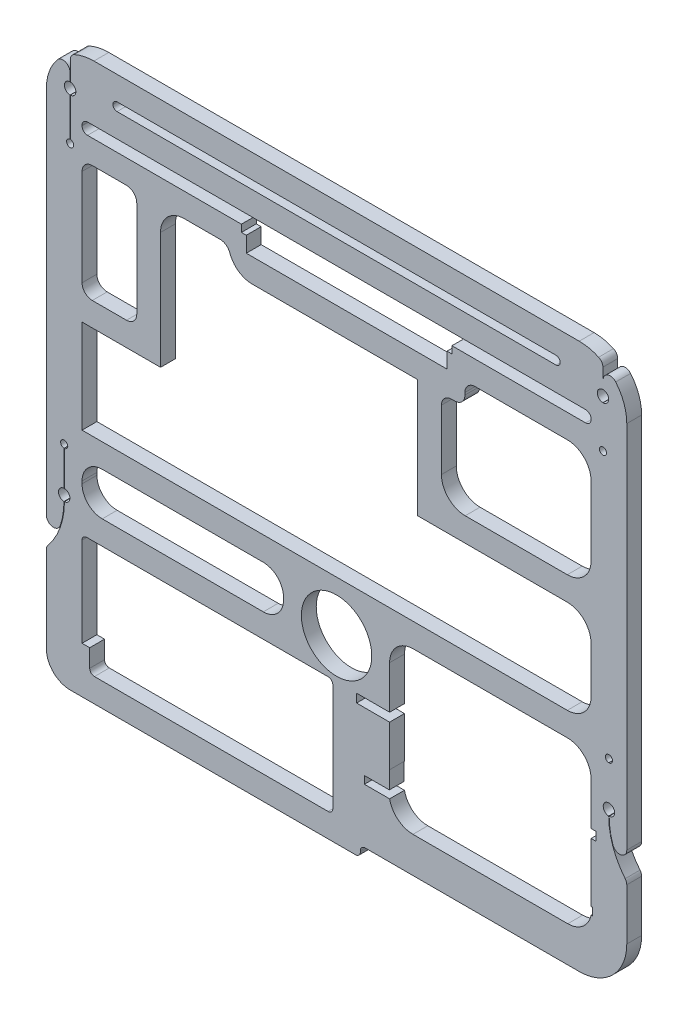
SolidWorks part; units mm, degrees
ref_plane "Front Plane" through (0, 0, 0) normal (0, 0, 1) x (1, 0, 0)
ref_plane "Top Plane" through (0, 0, 0) normal (0, 1, 0) x (1, 0, 0)
ref_plane "Right Plane" through (0, 0, 0) normal (1, 0, 0) x (0, 0, -1)
sketch "Sketch1" plane through (0, 0, 0) normal (0, 0, 1) x (1, 0, 0)
  line L0 (63.9883, 61.406) -> (63.9883, 57.596) construction
  line L1 (11.1776, 3.1158) -> (73.1542, 3.1158)
  line L2 (11.1776, 3.1158) -> (11.1776, 61.406)
  line L3 (11.1776, 61.406) -> (73.1542, 61.406)
  line L4 (73.1542, 3.1158) -> (73.1542, 61.406)
  line L5 (69.3442, 57.596) -> (14.9876, 57.596)
  line L6 (69.3442, 57.596) -> (69.3442, 6.9258)
  line L7 (69.3442, 6.9258) -> (14.9876, 6.9258)
  line L8 (14.9876, 57.596) -> (14.9876, 6.9258)
  line L9 (63.9883, 59.501) -> (18.0707, 59.501) construction
  line L10 (14.9876, 39.3805) -> (11.1776, 39.3805) construction
  line L11 (13.0826, 39.3805) -> (13.0826, 23.9527) construction
  line L12 (13.5248, 6.9258) -> (13.5248, 3.1158) construction
  line L13 (13.5248, 5.0208) -> (21.1598, 5.0208) construction
  line L14 (73.1542, 38.1916) -> (69.3442, 38.1916) construction
  line L15 (71.2492, 38.1916) -> (71.2492, 22.3321) construction
  line L16 (55.7422, 59.501) -> (30.5962, 59.501) construction
  line L19 (42.3087, 5.0208) -> (41.7626, 5.0208) construction
  line L21 (69.3442, 27.6227) -> (69.3442, 52.516) construction
  line L22 (14.9876, 47.563) -> (14.9876, 27.6227) construction
  dimension "D1" = 3.81
  dimension "D2" = 3.81
extrude "Boss-Extrude1" add sketch "Sketch1" along normal blind 1.5875
sketch "Sketch2" plane through (0, 0, 0) normal (0, 0, -1) x (-1, 0, 0)
  line L0 (-69.3442, 6.9258) -> (-69.3442, 57.596) construction
  line L1 (-69.3442, 26.6348) -> (-14.9876, 26.6348)
  line L2 (-69.3442, 26.6348) -> (-69.3442, 24.0948)
  line L3 (-69.3442, 24.0948) -> (-14.9876, 24.0948)
  line L4 (-14.9876, 26.6348) -> (-14.9876, 24.0948)
  line L5 (-14.9876, 57.596) -> (-14.9876, 6.9258) construction
  line L6 (-20.1206, 26.6348) -> (-57.8206, 26.6348) construction
  line L7 (-53.9642, 53.4304) -> (-53.9642, 51.7667)
  line L8 (-32.5266, 53.4304) -> (-32.0059, 53.4304)
  line L9 (-32.5266, 51.7667) -> (-53.9642, 51.7667) construction
  line L10 (-32.5266, 51.7667) -> (-32.5266, 53.4304) construction
  line L11 (-69.3442, 54.1924) -> (-54.4849, 54.1924)
  line L12 (-69.3442, 54.1924) -> (-69.3442, 51.6524)
  line L13 (-69.3442, 51.6524) -> (-55.8692, 51.6524)
  line L14 (-14.9876, 54.1924) -> (-14.9876, 51.6524)
  line L15 (-69.3442, 57.596) -> (-14.9876, 57.596)
  line L16 (-69.3442, 57.596) -> (-69.3442, 55.4243)
  line L17 (-69.3442, 55.4243) -> (-14.9876, 55.4243)
  line L18 (-14.9876, 57.596) -> (-14.9876, 55.4243)
  line L19 (-69.3442, 57.596) -> (-14.9876, 57.596) construction
  line L20 (-54.4849, 54.1924) -> (-54.4849, 53.4304)
  line L21 (-62.3462, 55.4243) -> (-23.9922, 55.4243) construction
  line L22 (-54.4849, 53.4304) -> (-53.9642, 53.4304)
  line L23 (-32.5266, 51.7667) -> (-53.9642, 51.7667)
  line L24 (-32.5266, 51.7667) -> (-32.5266, 53.4304)
  line L25 (-55.8692, 51.6524) -> (-55.8692, 49.2267)
  line L26 (-55.8692, 49.2267) -> (-30.6216, 49.2267)
  line L27 (-30.6216, 49.2267) -> (-30.6216, 51.6524)
  line L28 (-30.6216, 51.6524) -> (-14.9876, 51.6524)
  line L29 (-32.0059, 53.4304) -> (-32.0059, 54.1924)
  line L30 (-62.3462, 54.1924) -> (-23.9922, 54.1924) construction
  line L32 (-54.4849, 53.4304) -> (-54.4849, 54.1924) construction
  line L33 (-32.0059, 53.4304) -> (-54.4849, 53.4304) construction
  line L34 (-32.0059, 54.1924) -> (-14.9876, 54.1924)
  line L36 (-32.0059, 53.4304) -> (-32.0059, 54.1924) construction
  line L37 (-32.5266, 51.7667) -> (-32.5266, 53.4304) construction
  dimension "D1" = 2.54
  dimension "D2" = 1.905
  dimension "D3" = 2.54
  dimension "D4" = 1.905
  dimension "D5" = 2.54
extrude "Boss-Extrude2" add sketch "Sketch2" against normal up to surface (1.5875 mm away) up to face at (42.1659, 32.2609, 1.5875)
sketch "Sketch3" plane through (0, 0, 0) normal (0, 0, -1) x (-1, 0, 0)
  line L0 (-57.8206, 36.6348) -> (-50.8206, 36.6348) construction
  line L1 (-57.8206, 36.6348) -> (-50.8206, 36.6348)
  line L2 (-57.8206, 36.6348) -> (-69.3442, 36.6348)
  line L3 (-69.3442, 26.6348) -> (-69.3442, 51.6524) construction
  line L4 (-69.3442, 36.6348) -> (-69.3442, 39.1748)
  line L5 (-69.3442, 39.1748) -> (-53.3606, 39.1748)
  line L6 (-50.8206, 28.408) -> (-50.8206, 36.6348)
  line L7 (-50.8206, 28.408) -> (-50.8206, 49.2267)
  line L8 (-55.8692, 49.2267) -> (-30.6216, 49.2267) construction
  line L9 (-50.8206, 49.2267) -> (-53.3606, 49.2267)
  line L10 (-53.3606, 49.2267) -> (-53.3606, 39.1748)
  line L11 (-23.3706, 36.6348) -> (-20.1206, 36.6348) construction
  line L12 (-23.3706, 36.6348) -> (-20.1206, 36.6348)
  line L13 (-20.1206, 36.6348) -> (-14.9876, 36.6348)
  line L14 (-14.9876, 51.6524) -> (-14.9876, 26.6348) construction
  line L15 (-14.9876, 36.6348) -> (-14.9876, 39.1748)
  line L16 (-14.9876, 39.1748) -> (-20.8306, 39.1748)
  line L17 (-20.8306, 39.1748) -> (-20.8306, 51.6524)
  line L18 (-30.6216, 51.6524) -> (-14.9876, 51.6524) construction
  line L19 (-20.8306, 51.6524) -> (-23.3706, 51.6524)
  line L20 (-23.3706, 51.6524) -> (-23.3706, 36.6348)
  line L21 (-23.3706, 36.6348) -> (-16.2412, 25.8471)
  line M22 (-69.3442, 26.6348) -> (-69.3442, 51.6524)
  line M25 (-55.8692, 49.2267) -> (-30.6216, 49.2267)
  line M27 (-30.6216, 51.6524) -> (-14.9876, 51.6524)
  line M28 (-14.9876, 51.6524) -> (-14.9876, 26.6348)
  dimension "D1" = 2.54
  dimension "D2" = 2.54
  dimension "D3" = 2.54
  dimension "D4" = 2.54
extrude "Boss-Extrude3" add sketch "Sketch3" against normal up to surface (1.5875 mm away) contours L10 L5 L2 L1 L6 L7 M25 M22 | L20 L12 L13 L16 L17 M27 M28 region at (63.5824, 36.8588, 0) region at (20.9265, 42.3962, 0) up to face at (42.8855, 53.7395, 1.5875)
sketch "Sketch4" plane through (0, 0, 0) normal (0, 0, -1) x (-1, 0, 0)
  line L0 (-69.3442, 24.0948) -> (-14.9876, 24.0948) construction
  line L1 (-47.8301, 24.0948) -> (-36.5017, 24.0948)
  line L2 (-47.8301, 24.0948) -> (-47.8301, 6.9258)
  line L3 (-47.8301, 6.9258) -> (-36.5017, 6.9258)
  line L4 (-36.5017, 24.0948) -> (-36.5017, 6.9258)
  line L5 (-14.9876, 6.9258) -> (-69.3442, 6.9258) construction
  line L6 (-45.9251, 21.2246) -> (-47.8301, 21.2246) construction
  line L7 (-38.4067, 21.2246) -> (-36.5017, 21.2246) construction
  circle A0 centre (-42.1659, 21.2246) radius 3.7592 construction
  dimension "D1" = 1.905
extrude "Boss-Extrude4" add sketch "Sketch4" against normal up to surface (1.5875 mm away) up to face at (17.9091, 45.4136, 1.5875)
sketch "Sketch5" plane through (0, 0, 0) normal (0, 0, -1) x (-1, 0, 0)
  line L0 (-15.8038, 16.9715) -> (-41.7626, 16.9715) construction
  line L3 (-41.7626, 4.5128) -> (-41.7626, 16.9715) construction
  line L4 (-15.8038, 4.5128) -> (-41.7626, 4.5128) construction
  line L5 (-15.8038, 4.5128) -> (-15.8038, 16.9715) construction
  line L6 (-15.8038, 16.9715) -> (-41.7626, 16.9715)
  line L7 (-41.7626, 4.5128) -> (-41.7626, 16.9715)
  line L8 (-15.8038, 4.5128) -> (-41.7626, 4.5128)
  line L9 (-15.8038, 4.5128) -> (-15.8038, 16.9715)
  circle A0 centre (-42.1659, 21.2246) radius 3.7592 construction
  circle A1 centre (-42.1659, 21.2246) radius 3.7592
extrude "Cut-Extrude1" cut sketch "Sketch5" against normal up to surface (1.5875 mm away) up to face at (58.5871, 15.5103, 1.5875)
sketch "Sketch8" plane through (0, 0, 0) normal (0, 0, -1) x (-1, 0, 0)
  line L1 (-36.5017, 16.9715) -> (-14.9876, 16.9715)
  line L2 (-36.5017, 16.9715) -> (-36.5017, 19.5115)
  line L3 (-36.5017, 19.5115) -> (-14.9876, 19.5115)
  line L4 (-14.9876, 16.9715) -> (-14.9876, 19.5115)
  line L5 (-14.9876, 24.0948) -> (-14.9876, 6.9258) construction
  dimension "D1" = 2.54
extrude "Boss-Extrude5" add sketch "Sketch8" against normal up to surface (1.5875 mm away) up to face at (38.4067, 21.2246, 1.5875)
fillet "Fillet1" radius 5.08 3 edges at (73.1542, 3.1158, 0.7937) (11.1776, 61.406, 0.7937) (73.1542, 61.406, 0.7937)
fillet "Fillet2" radius 2.54 7 edges at (23.3706, 51.6524, 0.7937) (30.6216, 49.2267, 0.7937) (69.3442, 51.6524, 0.7937) (53.3606, 39.1748, 0.7937) (69.3442, 26.6348, 0.7937) (69.3442, 39.1748, 0.7937) (69.3442, 36.6348, 0.7937)
fillet "Fillet3" radius 1.0922 8 edges at (53.3606, 49.2267, 0.7937) (55.8692, 49.2267, 0.7937) (55.8692, 51.6524, 0.7937) (14.9876, 39.1748, 0.7937) (20.8306, 39.1748, 0.7937) (14.9876, 51.6524, 0.7937) (20.8306, 51.6524, 0.7937) (30.6216, 51.6524, 0.7937)
fillet "Fillet4" radius 0.5842 4 edges at (14.9876, 55.4243, 0.7937) (69.3442, 55.4243, 0.7937) (69.3442, 54.1924, 0.7937) (14.9876, 54.1924, 0.7937)
fillet "Fillet8" radius 2.159 4 edges at (36.5017, 19.5115, 0.7937) (36.5017, 24.0948, 0.7937) (14.9876, 24.0948, 0.7938) (14.9876, 19.5115, 0.7937)
sketch "Sketch6" plane through (0, 0, 0) normal (0, 0, -1) x (-1, 0, 0)
  line L0 (-16.6206, 28.1348) -> (-18.1206, 26.6348) construction
  line L1 (-18.1206, 36.6348) -> (-16.6206, 35.1348) construction
  line L2 (-16.6206, 35.1348) -> (-16.6206, 28.1348) construction
  line L3 (-16.6206, 28.1348) -> (-18.1206, 26.6348)
  line L4 (-18.1206, 36.6348) -> (-16.6206, 35.1348)
  line L5 (-16.6206, 35.1348) -> (-16.6206, 28.1348)
  line L6 (-18.1206, 36.6348) -> (-18.1206, 26.6348)
  circle A0 centre (-71.2492, 19.6852) radius 0.6096 construction
  circle A1 centre (-71.2492, 19.6852) radius 0.6096
  circle A4 centre (-70.6142, 57.596) radius 0.6096 construction
  circle A5 centre (-70.6142, 57.596) radius 0.6096
  circle A6 centre (-13.0826, 19.6852) radius 0.6096 construction
  circle A7 centre (-13.0826, 19.6852) radius 0.6096
  circle A10 centre (-13.7176, 57.596) radius 0.6096 construction
  circle A11 centre (-13.7176, 57.596) radius 0.6096
extrude "Cut-Extrude2" cut sketch "Sketch6" against normal up to surface (1.5875 mm away) up to face at (24.1846, 9.4701, 1.5875)
sketch "Sketch7" plane through (0, 0, 0) normal (0, 0, -1) x (-1, 0, 0)
  line L0 (-44.3026, 16.9715) -> (-69.8804, 16.9715) construction
  line L1 (-69.8804, 16.9715) -> (-69.8804, 16.0571) construction
  line L2 (-69.8804, 16.0571) -> (-44.3026, 16.0571) construction
  line L3 (-44.3026, 16.0571) -> (-44.3026, 16.9715) construction
  line L4 (-45.1366, 9.7751) -> (-69.5206, 9.7751) construction
  line L5 (-69.5206, 9.7751) -> (-69.5206, 8.9623) construction
  line L6 (-69.5206, 8.9623) -> (-45.1366, 8.9623) construction
  line L7 (-45.1366, 8.9623) -> (-45.1366, 9.7751) construction
  line L8 (-44.3026, 16.9715) -> (-69.8804, 16.9715)
  line L9 (-69.8804, 16.9715) -> (-69.8804, 16.0571)
  line L10 (-69.8804, 16.0571) -> (-44.3026, 16.0571)
  line L11 (-44.3026, 16.0571) -> (-44.3026, 16.9715)
  line L12 (-45.1366, 9.7751) -> (-69.5206, 9.7751)
  line L13 (-69.5206, 9.7751) -> (-69.5206, 8.9623)
  line L14 (-69.5206, 8.9623) -> (-45.1366, 8.9623)
  line L15 (-45.1366, 8.9623) -> (-45.1366, 9.7751)
  line L20 (-66.8536, 9.7751) -> (-47.8036, 9.7751)
  line L21 (-47.8036, 9.7751) -> (-47.8036, 11.6547)
  line L22 (-47.8036, 11.6547) -> (-66.8536, 11.6547)
  line L23 (-66.8536, 11.6547) -> (-66.8536, 9.7751)
  line L24 (-66.8536, 9.7751) -> (-47.8036, 9.7751)
  line L25 (-47.8036, 9.7751) -> (-47.8036, 11.6547)
  line L26 (-47.8036, 11.6547) -> (-66.8536, 11.6547)
  line L27 (-66.8536, 11.6547) -> (-66.8536, 9.7751)
  dimension "D1" = 0
extrude "Cut-Extrude3" cut sketch "Sketch7" against normal up to surface (1.5875 mm away) contours L14 L15 L12 L13 | L26 L27 L12 L25 | L10 L11 L8 L9 region at (57.0915, 16.5143, 0) region at (57.3286, 9.3687, 0) region at (57.3286, 10.7149, 0) up to face at (13.108, 57.596, 1.5875)
fillet "Fillet6" radius 0.508 4 edges at (41.7626, 16.9715, 0.7937) (41.7626, 4.5128, 0.7937) (15.8038, 4.5128, 0.7937) (14.9876, 16.9715, 0.7937)
sketch "Sketch9" plane through (0, 0, 1.5875) normal (0, 0, 1) x (1, 0, 0)
  line L0 (68.0742, 61.406) -> (16.2576, 61.406) construction
  line L1 (18.2896, 58.866) -> (66.0422, 58.866)
  line L2 (18.2896, 58.866) -> (18.2896, 57.9643)
  line L3 (18.2896, 57.9643) -> (66.0422, 57.9643)
  line L8 (66.0422, 58.866) -> (66.0422, 57.9643)
  line L9 (15.5718, 55.4243) -> (68.76, 55.4243) construction
  line L10 (11.1776, 56.326) -> (11.1776, 59.3208) construction
  line L11 (18.2896, 58.866) -> (11.1776, 58.866) construction
  line L13 (66.0422, 58.866) -> (73.1542, 58.866) construction
  line L14 (73.1542, 56.326) -> (73.1542, 56.8419) construction
  dimension "D1" = 2.54
  dimension "D2" = 2.54
  dimension "D3" = 7.112
extrude "Cut-Extrude4" cut sketch "Sketch9" against normal up to surface (1.5875 mm away) up to face at (57.106, 13.2916, 0)
fillet "Fillet7" radius 0.4318 4 edges at (18.2896, 57.9643, 0.7937) (18.2896, 58.866, 0.7937) (66.0422, 57.9643, 0.7937) (66.0422, 58.866, 0.7937)
fillet "Fillet9" radius 2.54 4 edges at (69.3442, 6.9258, 0.7937) (47.8301, 6.9258, 0.7937) (69.3442, 24.0948, 0.7937) (47.8301, 24.0948, 0.7937)
sketch "Sketch10" plane through (0, 0, 1.5875) normal (0, 0, 1) x (1, 0, 0)
  line L0 (42.1659, 24.9838) -> (42.1659, -13.4858) construction
  line L1 (11.1776, 3.1158) -> (44.7059, 3.1158)
  line L2 (11.1776, 3.1158) -> (11.1776, 1.9728)
  line L3 (11.1776, 1.9728) -> (44.7059, 1.9728)
  line L4 (44.7059, 3.1158) -> (44.7059, 1.9728)
  line L5 (16.3118, 4.5128) -> (41.2546, 4.5128) construction
  circle A0 centre (42.1659, 21.2246) radius 3.7592 construction
  dimension "D1" = 2.54
  dimension "D2" = 2.54
extrude "Boss-Extrude6" add sketch "Sketch10" against normal up to surface (1.5875 mm away) up to face at (42.1659, 58.4152, 0)
fillet "Fillet10" radius 2.54 1 edges at (11.1776, 1.9728, 0.7937)
fillet "Fillet11" radius 0.508 2 edges at (44.7059, 3.1158, 0.7937) (44.7059, 1.9728, 0.7937)
sketch "Sketch11" plane through (0, 0, 1.5875) normal (0, 0, 1) x (1, 0, 0)
  line L0 (13.7049, 59.0933) -> (13.7049, 58.2055) construction
  line L1 (13.7049, 56.9866) -> (13.7049, 52.8968) construction
  line L2 (13.7303, 52.8968) -> (13.7303, 56.9866) construction
  line L3 (13.7303, 58.2055) -> (13.7303, 60.2667) construction
  line L4 (70.6015, 58.2055) -> (70.6015, 60.2667) construction
  line L5 (70.6269, 56.9866) -> (70.6269, 52.8968) construction
  line L6 (70.6015, 52.8968) -> (70.6015, 56.9866) construction
  line L7 (71.2619, 24.0038) -> (71.2619, 20.2947) construction
  line L8 (71.2365, 24.0038) -> (71.2365, 20.2947) construction
  line L9 (13.0953, 24.0038) -> (13.0953, 20.2947) construction
  line L10 (13.0699, 24.0038) -> (13.0699, 20.2947) construction
  line L11 (13.7049, 59.0933) -> (13.7049, 58.2055)
  line L12 (13.7049, 56.9866) -> (13.7049, 52.8968)
  line L13 (13.7303, 52.8968) -> (13.7303, 56.9866)
  line L14 (13.7303, 58.2055) -> (13.7303, 60.2667)
  line L15 (70.6015, 58.2055) -> (70.6015, 60.2667)
  line L16 (70.6269, 56.9866) -> (70.6269, 52.8968)
  line L17 (70.6015, 52.8968) -> (70.6015, 56.9866)
  line L18 (71.2619, 24.0038) -> (71.2619, 20.2947)
  line L19 (71.2365, 24.0038) -> (71.2365, 20.2947)
  line L20 (13.0953, 24.0038) -> (13.0953, 20.2947)
  line L21 (13.0699, 24.0038) -> (13.0699, 20.2947)
  line L22 (73.1542, 8.1958) -> (73.1542, 56.326) construction
  line L23 (11.1776, 56.326) -> (11.1776, 4.5128) construction
  line L24 (73.1542, 13.6774) -> (73.1542, 16.8829)
  line L25 (11.1776, 16.8829) -> (11.1776, 13.6774)
  line L26 (70.6269, 59.0933) -> (70.6269, 58.2055) construction
  line L27 (70.6269, 59.0933) -> (70.6269, 58.2055)
  arc A0 (13.7049, 59.0933) -> (12.3579, 59.5817) centre (12.9429, 59.0933) ccw construction
  arc A1 (13.7049, 52.8968) -> (13.7303, 52.8968) centre (13.7176, 52.516) ccw construction
  arc A2 (14.1807, 60.9621) -> (13.7303, 60.2667) centre (14.4923, 60.2667) ccw construction
  arc A3 (70.6015, 60.2667) -> (70.151, 60.9621) centre (69.8395, 60.2667) ccw construction
  arc A4 (71.9738, 59.5817) -> (70.6269, 59.0933) centre (71.3889, 59.0933) ccw construction
  arc A5 (70.6015, 52.8968) -> (70.6269, 52.8968) centre (70.6142, 52.516) ccw construction
  arc A6 (71.2619, 24.0038) -> (71.2365, 24.0038) centre (71.2492, 24.3846) ccw construction
  arc A7 (71.2746, 19.0762) -> (71.6692, 16.6421) centre (78.975, 19.0756) ccw construction
  arc A8 (71.6692, 16.6421) -> (73.1542, 16.8829) centre (72.3922, 16.8829) ccw construction
  arc A9 (71.2238, 19.0762) -> (72.9814, 14.1605) centre (78.975, 19.0756) ccw construction
  arc A10 (73.1542, 13.6774) -> (72.9814, 14.1605) centre (72.3922, 13.6774) ccw construction
  arc A11 (13.0953, 24.0038) -> (13.0699, 24.0038) centre (13.0826, 24.3846) ccw construction
  arc A12 (11.3503, 14.1605) -> (13.108, 19.0762) centre (5.3567, 19.0756) ccw construction
  arc A13 (12.6625, 16.6421) -> (13.0572, 19.0762) centre (5.3567, 19.0756) ccw construction
  arc A14 (11.1776, 16.8829) -> (12.6625, 16.6421) centre (11.9396, 16.8829) ccw construction
  arc A15 (11.3503, 14.1605) -> (11.1776, 13.6774) centre (11.9396, 13.6774) ccw construction
  arc A16 (13.7049, 59.0933) -> (12.3579, 59.5817) centre (12.9429, 59.0933) ccw
  arc A17 (13.7049, 52.8968) -> (13.7303, 52.8968) centre (13.7176, 52.516) ccw
  arc A18 (14.1807, 60.9621) -> (13.7303, 60.2667) centre (14.4923, 60.2667) ccw
  arc A19 (70.6015, 60.2667) -> (70.151, 60.9621) centre (69.8395, 60.2667) ccw
  arc A20 (71.9738, 59.5817) -> (70.6269, 59.0933) centre (71.3889, 59.0933) ccw
  arc A21 (70.6015, 52.8968) -> (70.6269, 52.8968) centre (70.6142, 52.516) ccw
  arc A22 (71.2619, 24.0038) -> (71.2365, 24.0038) centre (71.2492, 24.3846) ccw
  arc A23 (71.2746, 19.0762) -> (71.6692, 16.6421) centre (78.975, 19.0756) ccw
  arc A24 (71.6692, 16.6421) -> (73.1542, 16.8829) centre (72.3922, 16.8829) ccw
  arc A25 (71.2238, 19.0762) -> (72.9814, 14.1605) centre (78.975, 19.0756) ccw
  arc A26 (73.1542, 13.6774) -> (72.9814, 14.1605) centre (72.3922, 13.6774) ccw
  arc A27 (13.0953, 24.0038) -> (13.0699, 24.0038) centre (13.0826, 24.3846) ccw
  arc A28 (11.3503, 14.1605) -> (13.108, 19.0762) centre (5.3567, 19.0756) ccw
  arc A29 (12.6625, 16.6421) -> (13.0572, 19.0762) centre (5.3567, 19.0756) ccw
  arc A30 (11.1776, 16.8829) -> (12.6625, 16.6421) centre (11.9396, 16.8829) ccw
  arc A31 (11.3503, 14.1605) -> (11.1776, 13.6774) centre (11.9396, 13.6774) ccw
  arc A32 (16.2576, 61.406) -> (11.1776, 56.326) centre (16.2576, 56.326) ccw construction
  circle A33 centre (13.7176, 57.596) radius 0.6096 construction
  arc A34 (73.1542, 56.326) -> (68.0742, 61.406) centre (68.0742, 56.326) ccw construction
  circle A35 centre (70.6142, 57.596) radius 0.6096 construction
  circle A36 centre (71.2492, 19.6852) radius 0.6096 construction
  circle A37 centre (13.0826, 19.6852) radius 0.6096 construction
  arc A38 (14.1807, 60.9621) -> (12.3579, 59.5817) centre (16.2576, 56.326) ccw
  arc A39 (13.7303, 58.2055) -> (13.7049, 58.2055) centre (13.7176, 57.596) ccw
  arc A40 (71.9738, 59.5817) -> (70.151, 60.9621) centre (68.0742, 56.326) ccw
  arc A41 (70.6015, 56.9866) -> (70.6269, 56.9866) centre (70.6142, 57.596) ccw
  arc A42 (71.2619, 20.2947) -> (71.2365, 20.2947) centre (71.2492, 19.6852) ccw
  arc A43 (13.0572, 19.0762) -> (13.108, 19.0762) centre (13.0826, 19.6852) ccw
  arc A44 (13.0953, 20.2947) -> (13.0699, 20.2947) centre (13.0826, 19.6852) ccw
  arc A45 (13.7049, 56.9866) -> (13.7303, 56.9866) centre (13.7176, 57.596) ccw
  arc A46 (71.2238, 19.0762) -> (71.2746, 19.0762) centre (71.2492, 19.6852) ccw
  arc A47 (70.6015, 56.9866) -> (70.6269, 56.9866) centre (70.6142, 57.596) ccw
  arc A48 (70.6269, 58.2055) -> (70.6015, 58.2055) centre (70.6142, 57.596) ccw
extrude "Cut-Extrude5" cut sketch "Sketch11" against normal through all contours A39 L14 A18 A38 A16 L11 | A45 L12 A17 L13 | A43 A29 A30 L25 A31 A28 | A44 L20 A27 L21 | A46 A25 A26 L24 A24 A23 | A42 L18 A22 L19 | A48 L27 A20 A40 A19 L15 | A41 L17 A21 L16 region at (13.3996, 60.0409, 1.5875) region at (13.7176, 52.9661, 1.5875) region at (70.9321, 60.0409, 1.5875) region at (70.6142, 52.9661, 1.5875) region at (71.2492, 24.0019, 1.5875) region at (13.0826, 24.0019, 1.5875) region at (72.5827, 15.6068, 1.5875) region at (11.749, 15.6068, 1.5875)
